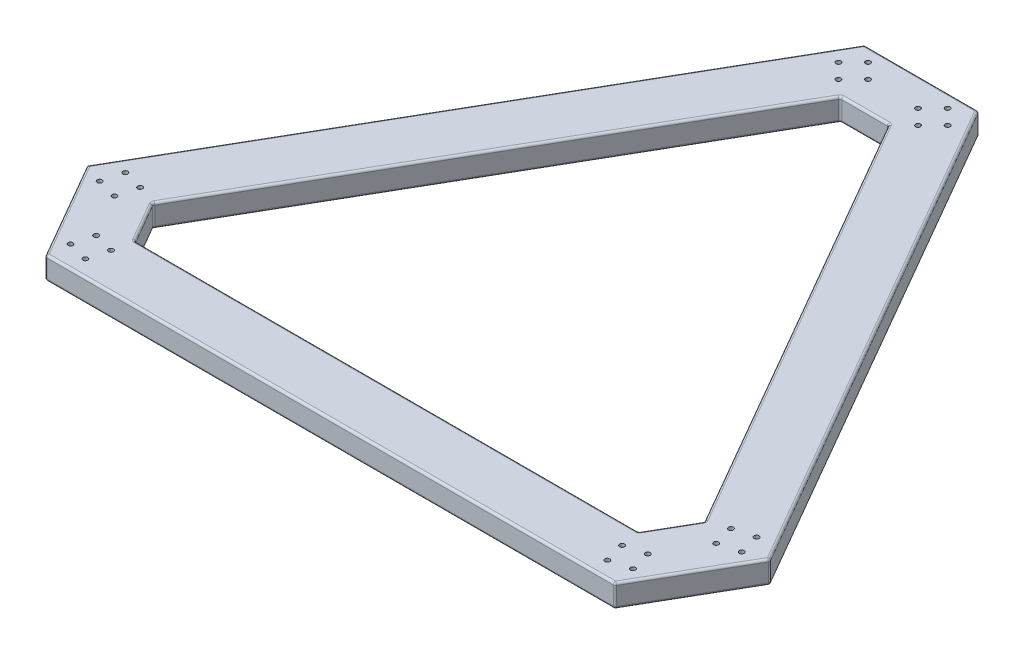
SolidWorks part; units mm, degrees
ref_plane "Front Plane" through (0, 0, 0) normal (0, 0, 1) x (1, 0, 0)
ref_plane "Top Plane" through (0, 0, 0) normal (0, 1, 0) x (1, 0, 0)
ref_plane "Right Plane" through (0, 0, 0) normal (1, 0, 0) x (0, 0, -1)
sketch "Sketch1" plane through (0, 0, 0) normal (0, 1, 0) x (1, 0, 0)
  line L0 (-275, -158.7713) -> (0, 0) construction
  line L1 (-50, 317.5426) -> (-300, -115.4701)
  line L2 (-250, -202.0726) -> (250, -202.0726)
  line L3 (300, -115.4701) -> (50, 317.5426)
  line L4 (250, -202.0726) -> (300, -115.4701)
  line L5 (50, 317.5426) -> (-50, 317.5426)
  line L6 (-300, -115.4701) -> (-250, -202.0726)
  line L7 (0, 0) -> (0, 317.5426) construction
  line L8 (0, 0) -> (275, -158.7713) construction
  circle A0 centre (0, 0) radius 202.0726 construction
  circle A1 centre (0, 0) radius 317.5426 construction
  circle A2 centre (-270.8494, -115.9604) radius 18
  circle A3 centre (-235.8494, -176.5822) radius 18
  circle A4 centre (-35, 292.5426) radius 18
  circle A5 centre (35, 292.5426) radius 18
  circle A6 centre (270.8494, -115.9604) radius 18
  circle A7 centre (235.8494, -176.5822) radius 18
  point P27 (0, 0)
  dimension "D1" = 36
  dimension "D4" = 500
  dimension "D2" = 25
  dimension "D3" = 35
  dimension "D5" = 100
extrude "Boss-Extrude1" add sketch "Sketch1" along normal blind 20 contours A2 | A3 | L1 L6 L2 L4 L3 L5 A7 A6 A5 A4 A3 A2 | A7 | A6 | A5 | A4 region at (0, 0, 0) region at (-270.8494, 0, 115.9604) region at (-235.8494, 0, 176.5822) region at (-35, 0, -292.5426) region at (35, 0, -292.5426) region at (270.8494, 0, 115.9604) region at (235.8494, 0, 176.5822)
extrude "Cut-Extrude1" cut sketch "Sketch1<3>" along normal blind 10 contours A2 | A3 | A7 | A6 | A5 | A4 region at (-270.8494, 0, 115.9604) region at (-235.8494, 0, 176.5822) region at (-35, 0, -292.5426) region at (35, 0, -292.5426) region at (270.8494, 0, 115.9604) region at (235.8494, 0, 176.5822)
sketch "Sketch1<3>" plane through (0, 0, 0) normal (0, 1, 0) x (1, 0, 0) same geometry as "Sketch1"
sketch "Sketch2" plane through (0, 0, 0) normal (0, -1, 0) x (1, 0, 0)
  line L0 (-242.265, 115.4701) -> (-221.1325, 152.0726)
  line L1 (-221.1325, 152.0726) -> (221.1325, 152.0726)
  line L2 (221.1325, 152.0726) -> (242.265, 115.4701)
  line L3 (242.265, 115.4701) -> (21.1325, -267.5426)
  line L4 (21.1325, -267.5426) -> (-21.1325, -267.5426)
  line L5 (-21.1325, -267.5426) -> (-242.265, 115.4701)
  line L6 (-250, 202.0726) -> (250, 202.0726) construction
  line L7 (250, 202.0726) -> (300, 115.4701) construction
  line L8 (300, 115.4701) -> (50, -317.5426) construction
  line L9 (50, -317.5426) -> (-50, -317.5426) construction
  line L10 (-50, -317.5426) -> (-300, 115.4701) construction
  line L11 (-300, 115.4701) -> (-250, 202.0726) construction
  dimension "D1" = 50
  dimension "D2" = 50
  dimension "D3" = 50
  dimension "D4" = 50
extrude "Cut-Extrude2" cut sketch "Sketch2" against normal through all
fillet "Fillet1" radius 2 42 edges at (0, 20, -317.5426) (175, 20, -101.0363) (275, 20, 158.7713) (0, 20, 202.0726) (-275, 20, 158.7713) (-175, 20, -101.0363) (-231.6987, 20, 133.7713) (0, 20, 152.0726) (231.6987, 20, 133.7713) (131.6987, 20, -76.0363) (0, 20, -267.5426) (-131.6987, 20, -76.0363) (-35, 0, -274.5426) (270.8494, 0, 133.9604) (-235.8494, 0, 194.5822) (-275, 0, 158.7713) (0, 0, 202.0726) (275, 0, 158.7713) (175, 0, -101.0363) (0, 0, -317.5426) (-175, 0, -101.0363) (-270.8494, 0, 133.9604) (235.8494, 0, 194.5822) (35, 0, -274.5426) (131.6987, 0, -76.0363) (231.6987, 0, 133.7713) (0, 0, 152.0726) (-231.6987, 0, 133.7713) (-131.6987, 0, -76.0363) (0, 0, -267.5426) (21.1325, 10, -267.5426) (-21.1325, 10, -267.5426) (242.265, 10, 115.4701) (221.1325, 10, 152.0726) (-221.1325, 10, 152.0726) (-242.265, 10, 115.4701) (250, 10, 202.0726) (300, 10, 115.4701) (50, 10, -317.5426) (-50, 10, -317.5426) (-250, 10, 202.0726) (-300, 10, 115.4701)
hole_wizard "M4 Clearance Hole1" positions "Sketch4" profile "Sketch3" hole size "M4" standard "ISO" end condition through all
sketch "Sketch4" plane through (0, 10, 0) normal (0, -1, 0) x (-1, 0, 0)
  line L0 (35, 274.5426) -> (35, 310.5426) construction
  line L2 (53, 292.5426) -> (17, 292.5426) construction
  line L4 (17, 292.5426) -> (-53, 292.5426) construction
  line L6 (-35, 274.5426) -> (-35, 310.5426) construction
  line L9 (-235.8494, -176.5822) -> (-270.8494, -115.9604) construction
  line L11 (-257.8752, -108.4698) -> (-279.472, -120.9387) construction
  line L13 (-224.971, -170.3016) -> (-246.7277, -182.8628) construction
  line L15 (235.8494, -176.5822) -> (270.8494, -115.9604) construction
  line L17 (279.185, -120.773) -> (262.5138, -111.1479) construction
  line L19 (248.4493, -183.8568) -> (223.2495, -169.3077) construction
  circle A0 centre (35, 292.5426) radius 18 construction
  circle A1 centre (-35, 292.5426) radius 18 construction
  point P0 (-35, 279.5426)
  point P2 (-35, 305.5426)
  point P4 (-48, 292.5426)
  point P6 (-22, 292.5426)
  point P8 (35, 279.5426)
  point P10 (35, 305.5426)
  point P12 (22, 292.5426)
  point P14 (48, 292.5426)
  point P51 (264.3494, -127.2188)
  point P53 (277.3494, -104.7021)
  point P55 (259.591, -109.4604)
  point P57 (282.1077, -122.4604)
  point P59 (229.3494, -187.8405)
  point P61 (247.1077, -183.0822)
  point P63 (224.591, -170.0822)
  point P65 (242.3494, -165.3239)
  point P67 (-247.1077, -183.0822)
  point P69 (-224.591, -170.0822)
  point P71 (-229.3494, -187.8405)
  point P73 (-242.3494, -165.3239)
  point P75 (-259.591, -109.4604)
  point P77 (-277.3494, -104.7021)
  point P79 (-264.3494, -127.2188)
  point P81 (-282.1077, -122.4604)
  dimension "D1" = 13
  dimension "D2" = 13
  dimension "D3" = 13
  dimension "D4" = 13
  dimension "D5" = 13
  dimension "D6" = 13
  dimension "D7" = 13
  dimension "D8" = 13
  dimension "D9" = 13
  dimension "D10" = 13
  dimension "D11" = 13
  dimension "D12" = 13
sketch "Sketch3" plane through (35, 10, -279.5426) normal (1, 0, 0) x (0, 0, -1)
  line L0 (0, 0) -> (0, 10)
  line L1 (0, 10) -> (2.15, 10)
  line L2 (2.15, 10) -> (2.15, 0)
  line L5 (2.15, 0) -> (0, 0)
  line L11 (0, -6.35) -> (0, 107.95) construction
  dimension "Thru Hole Dia." = 4.3
  dimension "Thru Hole Depth" = 10
